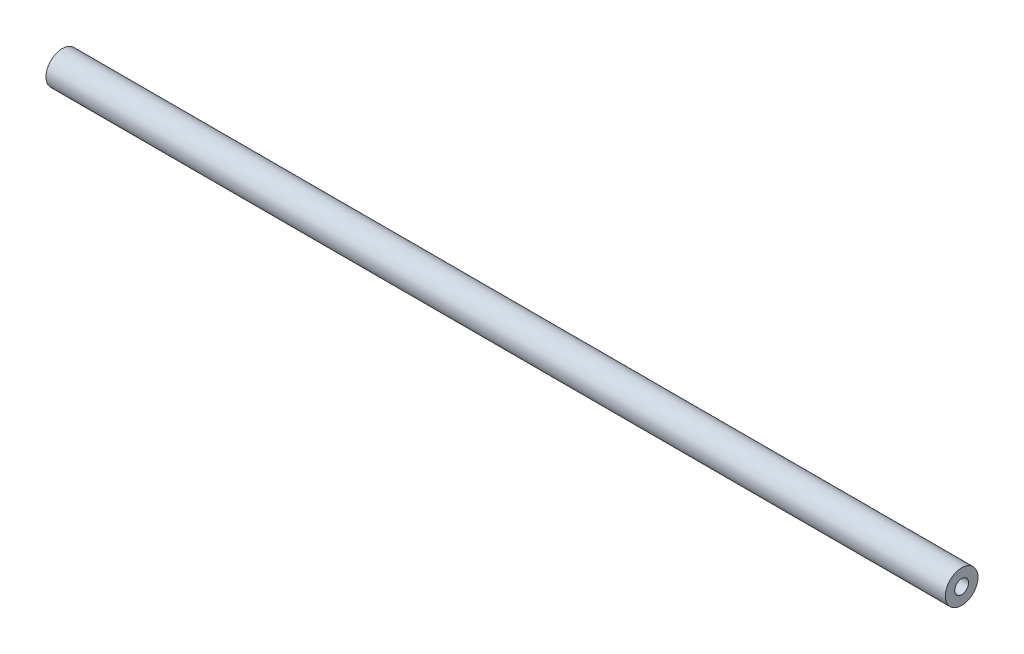
SolidWorks part; units mm, degrees
material "7075-T6 (SN)"
ref_plane "Front Plane" through (0, 0, 0) normal (0, 0, 1) x (1, 0, 0)
ref_plane "Top Plane" through (0, 0, 0) normal (0, 1, 0) x (1, 0, 0)
ref_plane "Right Plane" through (0, 0, 0) normal (1, 0, 0) x (0, 0, -1)
sketch "Sketch1" plane through (0, 0, 0) normal (1, 0, 0) x (0, 0, -1)
  circle A1 centre (0, 0) radius 4.7625
  dimension "D1" = 9.525
extrude "Boss-Extrude1" add sketch "Sketch1" along normal mid plane 261.9375 contours A1 region at (0, 0, 0)
hole_wizard "#10-32 Tapped Hole1" positions "3DSketch1" profile "Sketch2" tap size "#10-32" standard "ANSI Inch"
sketch3d "3DSketch1"
  line L0 (130.9688, 0, 0) -> (-130.9688, 0, 0) construction
  point P0 (130.9688, 0, 0)
  point P7 (-130.9688, 0, 0)
sketch "Sketch2" plane through (130.9688, 0, 0) normal (0, 1, 0) x (0, 0, -1)
  line L0 (0, 0) -> (0, 13.2428)
  line L1 (0, 13.2428) -> (2.0193, 12.0294)
  line L2 (2.0193, 12.0294) -> (2.0193, 0)
  line L5 (2.0193, 0) -> (0, 0)
  line L10 (0, 13.2428) -> (-2.0193, 12.0294) construction
  line L11 (0, -6.35) -> (0, 107.95) construction
  dimension "Tap Drill Dia." = 4.0386
  dimension "Tap Drill Depth" = 12.0294
  dimension "Drill Angle" = 118
cosmetic thread "Hole Thread1"
cosmetic thread "Hole Thread2"
